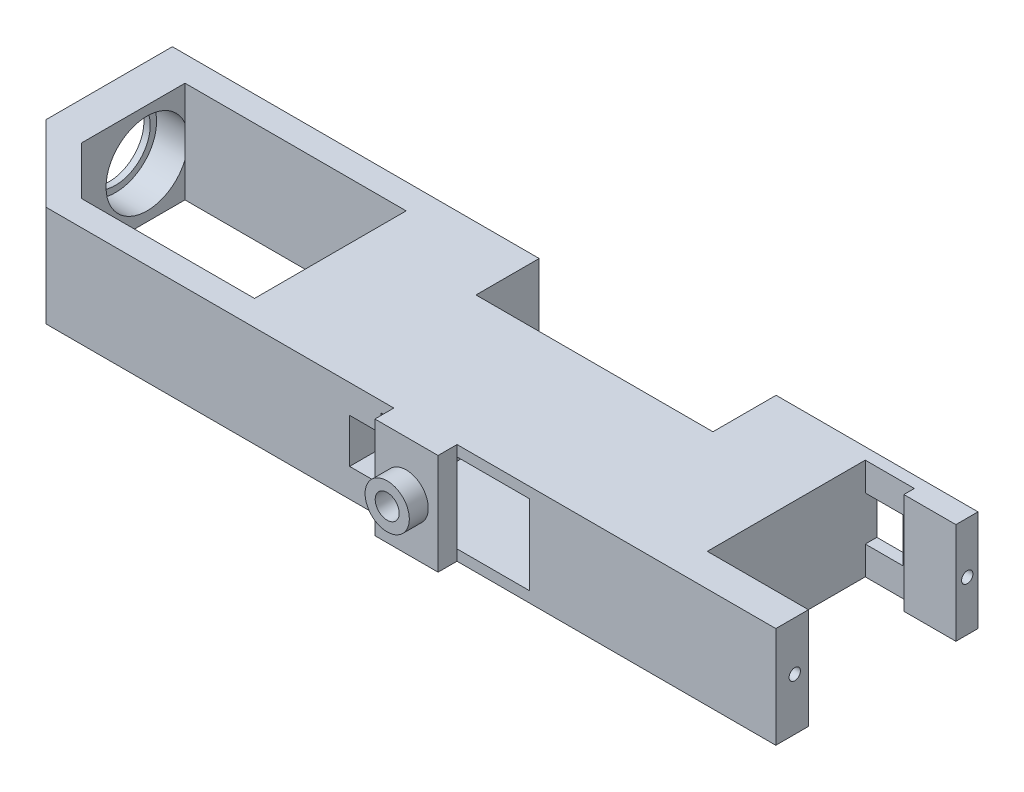
SolidWorks part; units mm, degrees
ref_plane "Front Plane" through (0, 0, 0) normal (0, 0, 1) x (1, 0, 0)
ref_plane "Top Plane" through (0, 0, 0) normal (0, 1, 0) x (1, 0, 0)
ref_plane "Right Plane" through (0, 0, 0) normal (1, 0, 0) x (0, 0, -1)
ref_axis "Axis1" through (8.5, 0, 50) along (0, 0, -1)
ref_axis "Axis2" through (88.99, 0, 0) along (-1, 0, 0)
sketch "Sketch1" plane through (0, 0, 0) normal (0, 1, 0) x (1, 0, 0)
  line L0 (64, -16.836) -> (47.9935, -16.836)
  line L1 (-63.5, 10) -> (64, 10)
  line L2 (-63.5, 10) -> (-63.5, -10)
  line L3 (-51.5, -22) -> (64, -22)
  line L4 (64, 10) -> (64, 6.5)
  line L5 (47.9935, -16.836) -> (47.9935, 8.164)
  line L6 (-63.5, -10) -> (-51.5, -22)
  line L8 (47.9935, 8.164) -> (55.7639, 8.164)
  line L9 (55.7639, 8.164) -> (55.7639, 6.5)
  line L10 (55.7639, 6.5) -> (64, 6.5)
  line L11 (64, -16.836) -> (64, -22)
  point P2 (-63.5, 0)
  dimension "D1" = 127.5
  dimension "D2" = 32
  dimension "D3" = 20
  dimension "D4" = 63.5
  dimension "D5" = 45
  dimension "D6" = 5.164
  dimension "D7" = 16.0065
  dimension "D8" = 25
  dimension "D9" = 3.5
  dimension "D10" = 8.2361
extrude "Boss-Extrude1" add sketch "Sketch1" along normal blind 8 and the other way blind 8
sketch "Sketch2" plane through (-63.5, 0, 0) normal (-1, 0, 0) x (0, 0, 1)
  circle A0 centre (0, 0) radius 5.5
  dimension "D1" = 11
extrude "Cut-Extrude1" cut sketch "Sketch2" against normal blind 8
sketch "Sketch3" plane through (0, 8, 0) normal (0, 1, 0) x (1, 0, 0)
  line L7 (-57.5, 6) -> (-22.5, 6)
  line L8 (-22.5, 6) -> (-22.5, -18)
  line L9 (-22.5, -18) -> (-49.8431, -18)
  line L10 (-49.8431, -18) -> (-57.5, -10.3431)
  line L11 (-57.5, -10.3431) -> (-57.5, 6)
  line L12 (-63.5, 10) -> (-63.5, -10) construction
  line L13 (-63.5, -10) -> (-51.5, -22) construction
  line L14 (64, 10) -> (-63.5, 10) construction
  line L15 (-51.5, -22) -> (64, -22) construction
  dimension "D1" = 6
  dimension "D2" = 4
  dimension "D3" = 4
  dimension "D4" = 4
  dimension "D5" = 35
extrude "Cut-Extrude2" cut sketch "Sketch3" against normal blind 16
sketch "Sketch4" plane through (-57.5, 0, 0) normal (1, 0, 0) x (0, 0, -1)
  circle A0 centre (0, 0) radius 6.5
  dimension "D1" = 13
extrude "Cut-Extrude3" cut sketch "Sketch4" against normal offset from surface (5 mm away) 1 contours A0 up to face at (-63.5, 0, 5.5)
sketch "Sketch5" plane through (0, 0, -10) normal (0, 0, -1) x (-1, 0, 0)
  line L0 (-64, 8) -> (63.5, 8) construction
  line L1 (-25.05, 6.3) -> (-1.55, 6.3)
  line L2 (-25.05, 6.3) -> (-25.05, -6.3)
  line L3 (-25.05, -6.3) -> (-1.55, -6.3)
  line L4 (-1.55, 6.3) -> (-1.55, -6.3)
  line L5 (-64, -8) -> (63.5, -8) construction
  line L6 (63.5, -8) -> (63.5, 8) construction
  dimension "D1" = 1.7
  dimension "D2" = 1.7
  dimension "D3" = 65.05
  dimension "D4" = 23.5
extrude "Cut-Extrude4" cut sketch "Sketch5" against normal through all
sketch "Sketch6" plane through (0, 0, -10) normal (0, 0, -1) x (-1, 0, 0)
  circle A0 centre (-0.2, 0) radius 0.9
  circle A1 centre (-27.5, 0) radius 0.9
  dimension "D1" = 1.8
  dimension "D2" = 1.8
extrude "Cut-Extrude5" cut sketch "Sketch6" against normal blind 17
sketch "Sketch7" plane through (0, 0, -10) normal (0, 0, -1) x (-1, 0, 0)
  line L0 (-64, -8) -> (63.5, -8) construction
  line L1 (-47.9935, 3.5) -> (-53.9935, 3.5)
  line L2 (-47.9935, 3.5) -> (-47.9935, -3.5)
  line L3 (-47.9935, -3.5) -> (-53.9935, -3.5)
  line L4 (-53.9935, 3.5) -> (-53.9935, -3.5)
  point P4 (-47.9935, 0)
  dimension "D1" = 7
  dimension "D2" = 6
  dimension "D3" = 8
  dimension "D4" = 0
extrude "Cut-Extrude6" cut sketch "Sketch7" against normal blind 7
sketch "Sketch8" plane through (0, 0, 22) normal (0, 0, 1) x (1, 0, 0)
  line L0 (1.55, -6.3) -> (1.55, 6.3) construction
  line L1 (1.55, -3.5) -> (-3.45, -3.5)
  line L2 (1.55, -3.5) -> (1.55, 3.5)
  line L3 (1.55, 3.5) -> (-3.45, 3.5)
  line L4 (-3.45, -3.5) -> (-3.45, 3.5)
  point P7 (1.55, 0)
  point P8 (1.55, 0)
  dimension "D1" = 5
  dimension "D2" = 7
extrude "Cut-Extrude7" cut sketch "Sketch8" against normal blind 10
sketch "Sketch9" plane through (64, 0, 0) normal (1, 0, 0) x (0, 0, -1)
  circle A0 centre (-18.9984, 0.247) radius 0.9
  circle A1 centre (8.2993, -0.1079) radius 0.9
  dimension "D1" = 1.8
  dimension "D2" = 1.8
extrude "Cut-Extrude8" cut sketch "Sketch9" against normal blind 7
sketch "Sketch10" plane through (0, 0, -10) normal (0, 0, -1) x (-1, 0, 0)
  line L0 (5.45, -8) -> (5.45, 8)
  line L1 (-64, -8) -> (63.5, -8) construction
  line L2 (-64, 8) -> (63.5, 8) construction
  line L3 (5.45, 8) -> (-32.05, 8)
  line L4 (-32.05, 8) -> (-32.05, -8)
  line L5 (-32.05, -8) -> (5.45, -8)
  line L6 (63.5, -8) -> (63.5, 8) construction
  line L7 (-64, -8) -> (-64, 8) construction
  dimension "D1" = 58.05
  dimension "D2" = 31.95
extrude "Cut-Extrude9" cut sketch "Sketch10" against normal blind 10
sketch "Sketch11" plane through (0, 0, 22) normal (0, 0, 1) x (1, 0, 0)
  line L0 (-51.5, -8) -> (64, -8) construction
  line L1 (3.55, -8) -> (13.55, -8)
  line L2 (3.55, -8) -> (3.55, 8)
  line L3 (3.55, 8) -> (13.55, 8)
  line L4 (13.55, -8) -> (13.55, 8)
  line L5 (-51.5, 8) -> (64, 8) construction
  line L6 (1.55, -6.3) -> (1.55, -3.5) construction
  dimension "D1" = 2
  dimension "D2" = 10
extrude "Boss-Extrude2" add sketch "Sketch11" along normal blind 3
sketch "Sketch12" plane through (0, 0, 25) normal (0, 0, 1) x (1, 0, 0)
  circle A0 centre (8.5, 0) radius 3.5
  circle A1 centre (8.5, 0) radius 1.9
  dimension "D1" = 7
  dimension "D2" = 3.8
extrude "Boss-Extrude3" add sketch "Sketch12" along normal blind 3
sketch "Sketch13" plane through (0, 0, 25) normal (0, 0, 1) x (1, 0, 0)
  circle A0 centre (8.5, 0) radius 1.9
  circle A1 centre (8.5, 0) radius 1.9 construction
extrude "Cut-Extrude10" cut sketch "Sketch13" against normal blind 3
